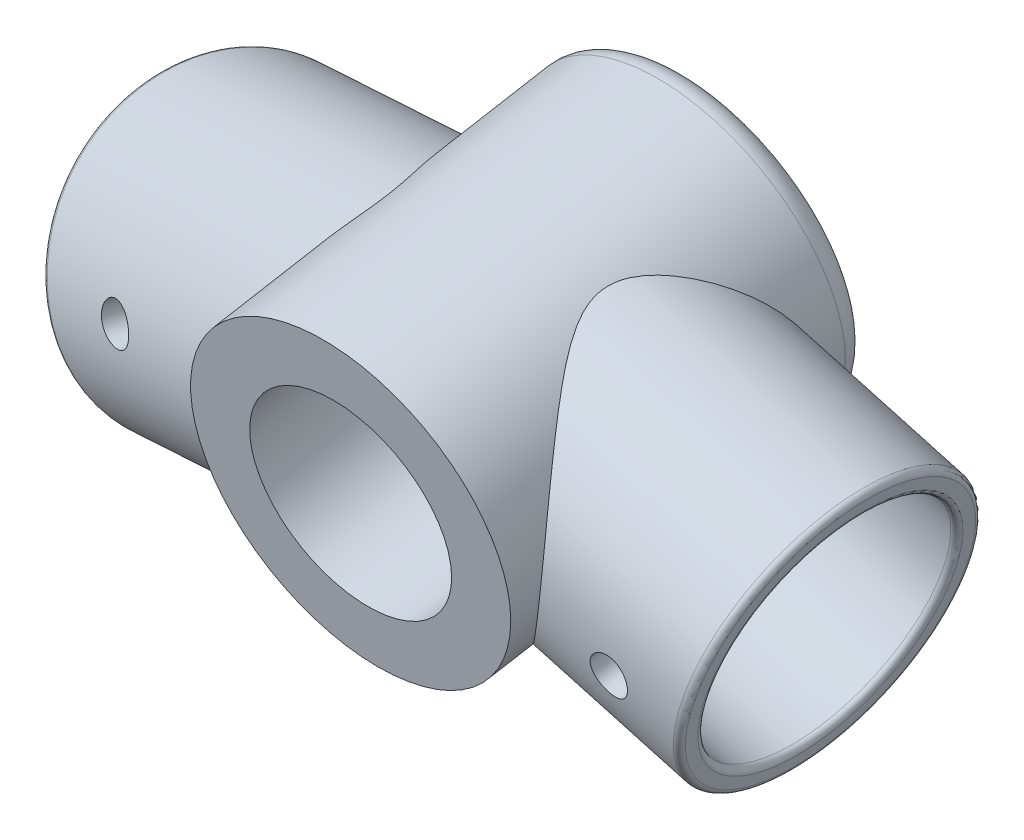
SolidWorks part; units mm, degrees
ref_plane "Front Plane" through (0, 0, 0) normal (0, 0, 1) x (1, 0, 0)
ref_plane "Top Plane" through (0, 0, 0) normal (0, 1, 0) x (1, 0, 0)
ref_plane "Right Plane" through (0, 0, 0) normal (1, 0, 0) x (0, 0, -1)
sketch "Sketch8" plane through (0, 0, 0) normal (0, 0, 1) x (1, 0, 0)
  line L0 (0, 0) -> (50000, 0) construction
ref_plane "Plane3" through (0, 0, 0) normal (0, 0.1736, 0.9848) x (1, 0, 0)
sketch "Sketch1" plane through (0, 0, 0) normal (0, 0.1736, 0.9848) x (1, 0, 0)
  circle A0 centre (0, 0) radius 13
  dimension "D1" = 26
extrude "Boss-Extrude1" add sketch "Sketch1" along normal blind 30
sketch "Sketch2" plane through (0, 0, 0) normal (0, 0.1736, 0.9848) x (1, 0, 0)
  circle A0 centre (0, 0) radius 8.2
  dimension "D1" = 16.4
extrude "Cut-Extrude1" cut sketch "Sketch2" along normal offset from surface (27 mm away) 3 up to face at (0, -7.5931, 31.8017)
sketch "Sketch3" plane through (0, 5.2094, 29.5442) normal (0, 0.1736, 0.9848) x (1, 0, 0)
  line L0 (0, 0) -> (0, -8) construction
  circle A2 centre (0, -4) radius 1.7
  circle A3 centre (0, 0) radius 8
  circle A4 centre (-3.4641, 2) radius 1.7
  circle A5 centre (3.4641, 2) radius 1.7
  point P7 (0, -4)
  point P13 (0, 0)
  dimension "D1" = 16
  dimension "D2" = 3.4
  dimension "D3" = 3
extrude "Cut-Extrude3" cut sketch "Sketch3" against normal through all contours A4 | A5 | A2 L0 | L0 A2 region at (0.7215, 1.2702, 30.2388) region at (-0.7215, 1.2702, 30.2388) region at (-3.4641, 7.1791, 29.1969) region at (3.4641, 7.1791, 29.1969)
sketch "Sketch7" plane through (0, 0, 0) normal (0, 0, 1) x (1, 0, 0)
  line L0 (0, 0) -> (24.0896, -6.6852) construction
  dimension "D1" = 25
  dimension "D2" = 15.51
ref_plane "Plane1" through (24.0896, -6.6852, 0) normal (0.9636, -0.2674, 0) x (0, 0, -1)
sketch "Sketch9" plane through (24.0896, -6.6852, 0) normal (0.9636, -0.2674, 0) x (0, 0, -1)
  line L0 (2.1776, 12.8163) -> (-27.3667, 17.8361) construction
  line L1 (2.1776, 12.8163) -> (-27.3667, 17.8361) construction
  line L2 (-12.5945, 15.3262) -> (-16.9497, -10.3065) construction
  line L3 (-31.7218, -7.7966) -> (-2.1776, -12.8163) construction
  circle A0 centre (-14.7721, 2.5099) radius 10.05
  circle A1 centre (-14.7721, 2.5099) radius 12.05
  dimension "D1" = 20.1
  dimension "D2" = 2
extrude "Boss-Extrude3" add sketch "Sketch9" against normal up to surface (17.3495 mm away) up to face at (0, -7.5931, 31.8017)
sketch "Sketch17" plane through (0, 0, 0) normal (0, 0.1736, 0.9848) x (1, 0, 0)
  line L0 (24.221, -6.6195) -> (12.5401, -3.4272) construction
  circle A0 centre (0, 0) radius 13 construction
  circle A1 centre (0, 0) radius 13 construction
  circle A2 centre (18.3806, -5.0233) radius 1.5875
  ellipse E0 centre (24.7608, -6.767) end of major axis (21.584, -18.3907) minor radius 0.5595 construction
  ellipse E1 centre (24.7608, -6.767) end of major axis (21.584, -18.3907) minor radius 0.5595 construction
  dimension "D1" = 3.175
extrude "Cut-Extrude4" cut sketch "Sketch17" against normal through all both and the other way through all
sketch "Sketch16" plane through (0, 0, 0) normal (0, 0, 1) x (1, 0, 0)
  line L0 (0, 0) -> (0, 50000) construction
ref_plane "Plane5" through (0, 0, 0) normal (0.2406, 0, 0.9706) x (0, 1, 0)
sketch "Sketch10" plane through (0, 0, 0) normal (-0.2406, 0, -0.9706) x (-0.9706, 0, 0.2406)
  line L2 (0, 0) -> (33.6442, -9.6473)
  dimension "D1" = 35
  dimension "D2" = 16
ref_plane "Plane4" through (-32.6558, -9.6473, 8.0951) normal (-0.933, -0.2756, 0.2313) x (0.2246, 0.0559, 0.9728)
sketch "Sketch14" plane through (-32.6558, -9.6473, 8.0951) normal (-0.933, -0.2756, 0.2313) x (0.2246, 0.0559, 0.9728)
  line L1 (-2.301, -0.419) -> (26.732, 4.8681) construction
  line L2 (12.1874, 15.4332) -> (12.1874, -10.9688) construction
  line L4 (26.7039, 18.0768) -> (-2.3291, 12.7897) construction
  circle A2 centre (12.1874, 2.2322) radius 10.05
  circle A3 centre (12.1874, 2.2322) radius 12.05
  ellipse E0 centre (0, 0) end of major axis (2.3291, -12.7897) minor radius 2.3388 construction
  ellipse E1 centre (29.033, 5.2871) end of major axis (31.3621, -7.5025) minor radius 2.3388 construction
  spline S0 degree 3 poles (17.3733, 10.0727) (16.4981, 10.2117) (16.059, 10.2419) (15.408, 10.2127) (15.192, 10.1906) (14.7621, 10.1197) (14.5521, 10.0713) (14.1459, 9.9522) (13.9489, 9.8812) (13.5653, 9.7191) (13.3778, 9.6274) (12.8374, 9.3305) (12.5042, 9.1036) (11.8713, 8.6083) (11.5715, 8.3391) (11.0047, 7.7779) (10.736, 7.4844) (9.9613, 6.571) (9.4861, 5.9186) (8.5913, 4.5325) (8.1704, 3.7933) (7.4057, 2.2724) (7.0588, 1.4866) (6.5963, 0.2641) (6.4511, -0.1531) (6.1876, -0.9881) (6.0688, -1.4067) (5.8588, -2.2459) (5.7674, -2.6678) (5.6163, -3.5087) (5.5577, -3.9215) (5.4752, -4.7313) (5.4514, -5.1282) (5.4435, -5.7108) (5.4456, -5.903) (5.4591, -6.2761) (5.4704, -6.4578) (5.5181, -6.9892) (5.5679, -7.3249) (5.669, -7.8013) (5.7071, -7.9556) (5.7922, -8.2552) (5.8394, -8.4009) (6.0936, -9.0964) (6.3556, -9.5547) (6.8243, -10.1204) (6.9935, -10.2881) (7.3478, -10.5788) (7.5339, -10.7031) (7.9227, -10.9142) (8.1256, -11.0011) (8.5477, -11.1407) (8.768, -11.1936) (9.4448, -11.3034) (9.9176, -11.3129) (10.9171, -11.2318) (11.4429, -11.1406) (12.3011, -10.9436) (12.598, -10.8681) (13.2163, -10.7038) (13.5385, -10.6148) (14.2256, -10.4297) (14.5941, -10.333) (15.1759, -10.1956) (15.3751, -10.1509) (15.7864, -10.0653) (15.999, -10.0243) (16.4245, -9.9489) (16.639, -9.9141) (17.071, -9.85) (17.2897, -9.8203) (17.9415, -9.7382) (18.365, -9.6926) (19.1961, -9.6036) (19.6033, -9.5601) (20.388, -9.466) (20.7683, -9.4152) (21.5106, -9.2989) (21.8725, -9.2334) (22.58, -9.0828) (22.9269, -8.9973) (23.9321, -8.7084) (24.5576, -8.4728) (25.4299, -8.0366) (25.7095, -7.8775) (26.2448, -7.5275) (26.5015, -7.3358) (27.2181, -6.7179) (27.6298, -6.2476) (28.2969, -5.161) (28.5407, -4.5624) (28.7548, -3.5737) (28.8002, -3.2276) (28.8355, -2.5252) (28.826, -2.1664) (28.7528, -1.4333) (28.6888, -1.0574) (28.5067, -0.2973) (28.3903, 0.081) (28.1108, 0.8341) (27.9477, 1.2089) (27.5768, 1.955) (27.3682, 2.3271) (26.6958, 3.4094) (26.1813, 4.0964) (25.3231, 5.0802) (25.0219, 5.4006) (24.4039, 6.0135) (24.0857, 6.3076) (23.1045, 7.1554) (22.4156, 7.6748) (21.3259, 8.3814) (20.9515, 8.6055) (20.1912, 9.0203) (19.8051, 9.2113) (19.018, 9.5556) (18.6171, 9.7091) (17.7947, 9.9674) (17.3733, 10.0727) (16.4981, 10.2117) (16.059, 10.2419) knots -0.015625 -0.015625 0 0 0.015625 0.015625 0.023438 0.023438 0.03125 0.03125 0.039063 0.039063 0.046875 0.046875 0.0625 0.0625 0.078125 0.078125 0.09375 0.09375 0.125 0.125 0.15625 0.15625 0.1875 0.1875 0.203125 0.203125 0.21875 0.21875 0.234375 0.234375 0.25 0.25 0.265625 0.265625 0.273438 0.273438 0.28125 0.28125 0.296875 0.296875 0.304688 0.304688 0.3125 0.3125 0.34375 0.34375 0.359375 0.359375 0.375 0.375 0.390625 0.390625 0.40625 0.40625 0.4375 0.4375 0.46875 0.46875 0.484375 0.484375 0.5 0.5 0.515625 0.515625 0.523438 0.523438 0.53125 0.53125 0.539063 0.539063 0.546875 0.546875 0.5625 0.5625 0.578125 0.578125 0.59375 0.59375 0.609375 0.609375 0.625 0.625 0.65625 0.65625 0.671875 0.671875 0.6875 0.6875 0.71875 0.71875 0.75 0.75 0.765625 0.765625 0.78125 0.78125 0.796875 0.796875 0.8125 0.8125 0.828125 0.828125 0.84375 0.84375 0.875 0.875 0.890625 0.890625 0.90625 0.90625 0.9375 0.9375 0.953125 0.953125 0.96875 0.96875 0.984375 0.984375 1 1 1.015625 1.015625 1.023438 only from (16.9357, 10.1422) to (16.9357, 10.1422) construction
  dimension "D1" = 20.1
  dimension "D2" = 2
extrude "Boss-Extrude4" add sketch "Sketch14" against normal up to surface (24.4707 mm away) up to face at (3.3545, -10.5761, 12.3488)
sketch "Sketch18" plane through (0, 0, 0) normal (0.2406, 0, 0.9706) x (0, 1, 0)
  line L0 (4.7595, 37.7752) -> (-18.4069, 31.1324) construction
  line L1 (4.7595, 37.7752) -> (-18.4069, 31.1324) construction
  line L2 (-6.8237, 34.4538) -> (5.2094, 7.1086) construction
  line L3 (-6.8237, 34.4538) -> (0.0342, 18.8694) construction
  circle A0 centre (-3.3948, 26.6616) radius 1.5875
  ellipse E1 centre (5.2094, 7.1086) end of major axis (15.6952, -0.5757) minor radius 12.4264 construction
  ellipse E2 centre (5.2094, 7.1086) end of major axis (15.6952, -0.5757) minor radius 12.4264 construction
  dimension "D1" = 3.175
extrude "Cut-Extrude5" cut sketch "Sketch18" against normal through all both and the other way through all
fillet "Fillet2" radius 0.5 4 edges at (27.983, 7.3445, 14.7721) (27.4482, 5.4173, 14.7721) (-27.1314, -18.38, 19.9732) (-27.6981, -16.4619, 19.9732)
fillet "Fillet3" radius 2 1 edges at (0, -7.5931, 31.8017)
mirror "Mirror1" about plane through (0, 0, 0) normal (0, 0, 1) of bodies 111 108
delete or keep bodies "Body-Delete/Keep 1" type delete bodies bodies 111
